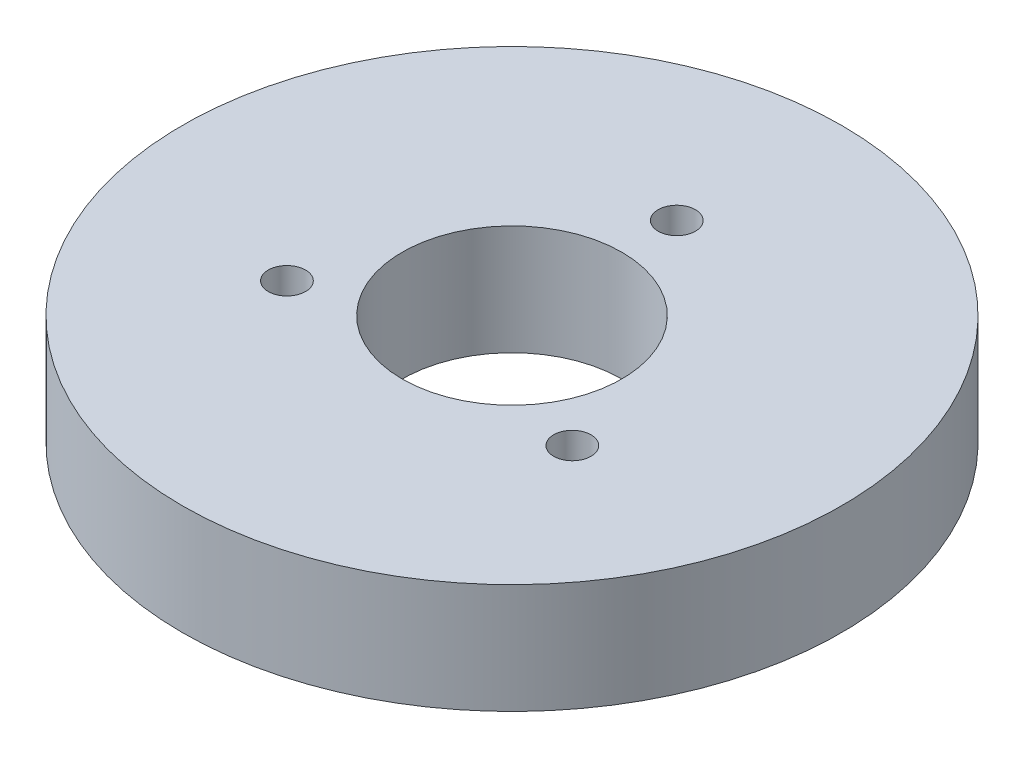
SolidWorks part; units mm, degrees
ref_plane "Front Plane" through (0, 0, 0) normal (0, 0, 1) x (1, 0, 0)
ref_plane "Top Plane" through (0, 0, 0) normal (0, 1, 0) x (1, 0, 0)
ref_plane "Right Plane" through (0, 0, 0) normal (1, 0, 0) x (0, 0, -1)
sketch "Sketch1" plane through (0, 0, 0) normal (0, 1, 0) x (1, 0, 0)
  circle A0 centre (0, 0) radius 10
  circle A1 centre (0, 0) radius 30
  dimension "D1" = 20
  dimension "D2" = 20
extrude "Boss-Extrude1" add sketch "Sketch1" along normal blind 10
hole_wizard "M3 Clearance Hole1" positions "Sketch2" profile "Sketch3" hole size "M3" standard "ANSI Metric" end condition through all
sketch "Sketch2" plane through (0, 10, 0) normal (0, 1, 0) x (1, 0, 0)
  circle A0 centre (0, 0) radius 15 construction
  point P0 (0, 15)
  point P14 (12.9919, -7.4991)
  point P15 (-12.9889, -7.5009)
  point P16 (0.001, 0)
  dimension "D2" = 30
  dimension "D1" = 15
  dimension "D3" = 3
sketch "Sketch3" plane through (0, 10, -15) normal (1, 0, 0) x (0, 0, 1)
  line L0 (0, 0) -> (0, 10)
  line L1 (0, 10) -> (1.7, 10)
  line L2 (1.7, 10) -> (1.7, 0)
  line L5 (1.7, 0) -> (0, 0)
  line L11 (0, -6.35) -> (0, 107.95) construction
  dimension "Thru Hole Dia." = 3.4
  dimension "Thru Hole Depth" = 10
